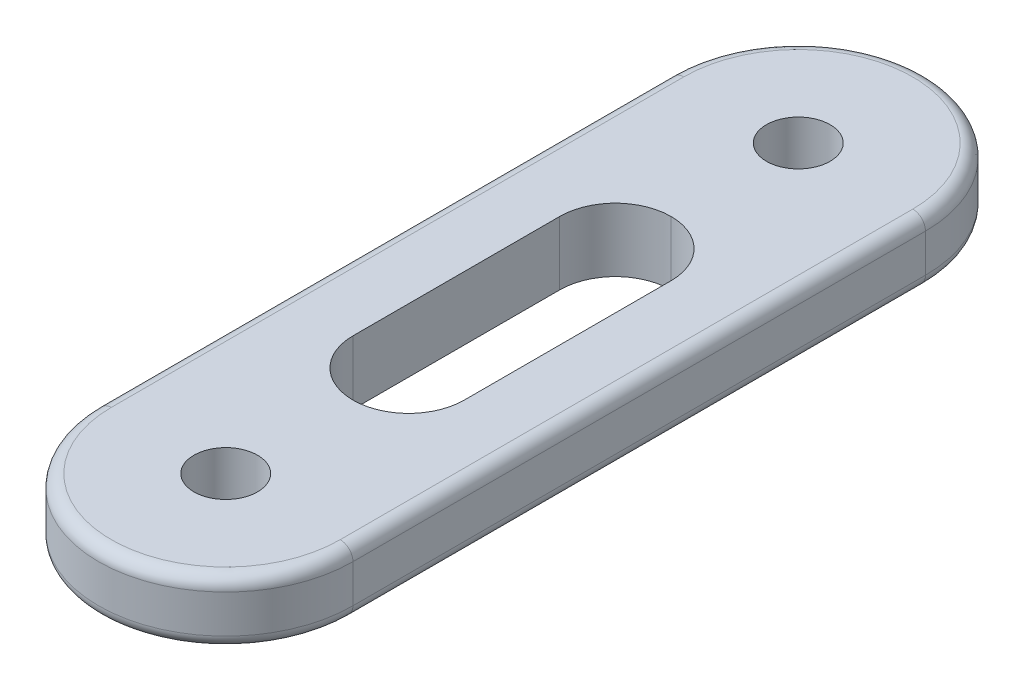
SolidWorks part; units mm, degrees
material "Cast Alloy Steel"
ref_plane "Front Plane" through (0, 0, 0) normal (0, 0, 1) x (1, 0, 0)
ref_plane "Top Plane" through (0, 0, 0) normal (0, 1, 0) x (1, 0, 0)
ref_plane "Right Plane" through (0, 0, 0) normal (1, 0, 0) x (0, 0, -1)
sketch "Sketch1" plane through (0, 0, 0) normal (0, 1, 0) x (1, 0, 0)
  line L0 (12.7, 82.55) -> (12.7, 0) construction
  line L1 (0, 0) -> (25.4, 0)
  line L2 (0, 0) -> (0, 82.55)
  line L3 (0, 82.55) -> (25.4, 82.55)
  line L4 (25.4, 0) -> (25.4, 82.55)
  line L5 (7.1437, 57.15) -> (18.2562, 57.15)
  line L6 (7.1437, 57.15) -> (7.1438, 25.4)
  line L7 (7.1438, 25.4) -> (18.2563, 25.4)
  line L8 (18.2562, 57.15) -> (18.2563, 25.4)
  circle A0 centre (12.7, 69.85) radius 3.175
  circle A1 centre (12.7, 12.7) radius 3.175
  point P11 (12.7, 57.15)
  dimension "D1" = 6.35
  dimension "D2" = 12.7
  dimension "D3" = 25.4
  dimension "D4" = 12.7
  dimension "D5" = 12.7
  dimension "D6" = 12.7
  dimension "D7" = 31.75
  dimension "D8" = 11.1125
extrude "Boss-Extrude1" add sketch "Sketch1" along normal blind 6.35
sketch "Sketch2" plane through (0, 6.35, 0) normal (0, 1, 0) x (1, 0, 0)
  line L0 (0, 0) -> (25.4, 0) construction
  line L1 (25.4, 82.55) -> (0, 82.55) construction
  circle A0 centre (12.7, 69.85) radius 12.7
  circle A1 centre (12.7, 12.7) radius 12.7
  line M3 (25.4, 82.55) -> (0, 82.55)
  line M5 (0, 0) -> (25.4, 0)
  line M13 (0, 82.55) -> (0, 0)
  line M14 (25.4, 0) -> (25.4, 82.55)
extrude "Cut-Extrude1" cut sketch "Sketch2" against normal through all contours A0 M3 M13 | A0 M14 M3 | A1 M13 M5 | A1 M5 M14 region at (22.5632, 6.35, -79.7132) region at (2.8368, 6.35, -79.7132) region at (22.5632, 6.35, -2.8368) region at (2.8368, 6.35, -2.8368)
fillet "Fillet1" radius 1.27 8 edges at (0, 6.35, -41.275) (0, 0, -41.275) (25.4, 0, -41.275) (25.4, 6.35, -41.275) (12.7, 0, 0) (12.7, 0, -82.55) (12.7, 6.35, 0) (12.7, 6.35, -82.55)
fillet "Fillet2" radius 5.5562 4 edges at (7.1438, 3.175, -25.4) (18.2563, 3.175, -25.4) (18.2562, 3.175, -57.15) (7.1437, 3.175, -57.15)
